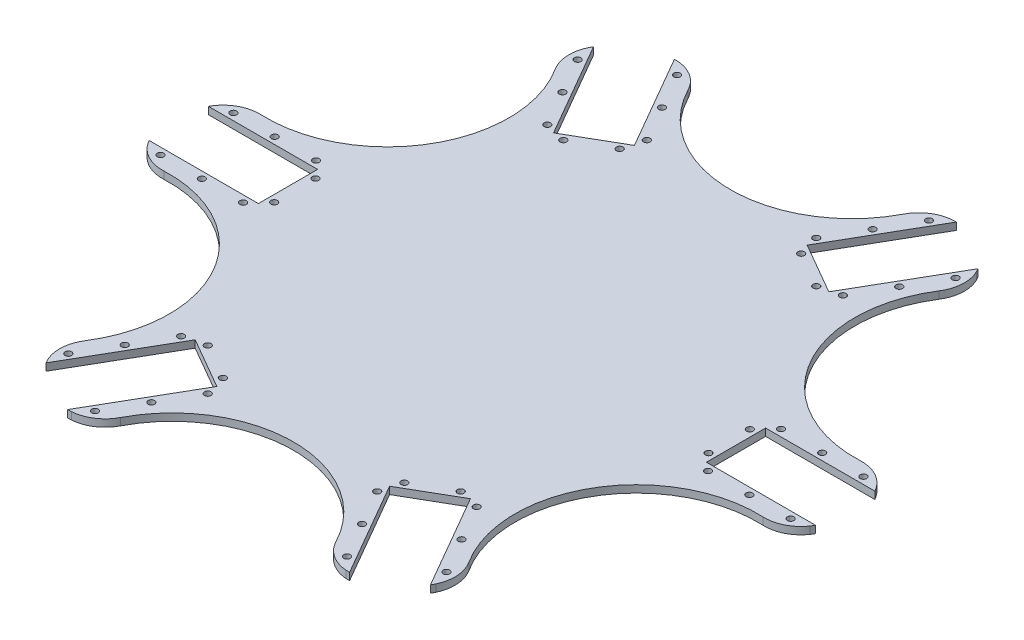
SolidWorks part; units mm, degrees
material "1060-H12"
ref_plane "Front Plane" through (0, 0, 0) normal (0, 0, 1) x (1, 0, 0)
ref_plane "Top Plane" through (0, 0, 0) normal (0, 1, 0) x (1, 0, 0)
ref_plane "Right Plane" through (0, 0, 0) normal (1, 0, 0) x (0, 0, -1)
sketch "Sketch2" plane through (0, 0, 0) normal (0, 1, 0) x (1, 0, 0)
  line L1 (0, 125) -> (-58.0814, 125)
  line L2 (-35.5814, 86.0289) -> (-56.7125, 73.8289)
  line L3 (-79.2125, 112.8) -> (-108.2532, 62.5)
  line L4 (-35.5814, 86.0289) -> (-58.0814, 125)
  line L7 (0, 0) -> (0, 125)
  line L8 (0, 0) -> (-108.2532, 62.5)
  line L12 (-79.2125, 112.8) -> (-56.7125, 73.8289)
  circle A0 centre (-37.3857, 81.754) radius 1.35
  circle A1 centre (-52.1082, 73.254) radius 1.35
  circle A2 centre (-60.8873, 75.4599) radius 1.35
  circle A3 centre (-34.9066, 90.4599) radius 1.35
  circle A4 centre (-51.9066, 119.9048) radius 1.35
  circle A5 centre (-43.4066, 105.1824) radius 1.35
  circle A6 centre (-69.3873, 90.1824) radius 1.35
  circle A7 centre (-77.8873, 104.9048) radius 1.35
  dimension "D3" = 3.5
  dimension "D5" = 2.8
  dimension "D9" = 34
  dimension "D13" = 2.8
  dimension "D14" = 2.8
  dimension "D2" = 3.5
  dimension "D4" = 17
  dimension "D6" = 2.8
  dimension "D12" = 17
  dimension "D15" = 17
  dimension "D16" = 34
extrude "Boss-Extrude1" add sketch "Sketch2" along normal blind 3
pattern_circular "CirPattern1" count 6 over 360 about axis through (0, 3, 0) along (0, -1, 0) of "Boss-Extrude1"
sketch "Sketch4" plane through (0, 3, 0) normal (0, 1, 0) x (1, 0, 0)
  line L0 (58.0814, 125) -> (-58.0814, 125) construction
  line L1 (137.2939, 12.2) -> (79.2125, 112.8) construction
  line L2 (79.2125, -112.8) -> (137.2939, -12.2) construction
  line L3 (-58.0814, -125) -> (58.0814, -125) construction
  line L4 (-137.2939, -12.2) -> (-79.2125, -112.8) construction
  line L5 (-79.2125, 112.8) -> (-137.2939, 12.2) construction
  line L6 (79.2125, -112.8) -> (137.2939, -12.2)
  line L8 (137.2939, 12.2) -> (79.2125, 112.8)
  line L10 (58.0814, 125) -> (-58.0814, 125)
  line L12 (-79.2125, 112.8) -> (-137.2939, 12.2)
  line L14 (-92.2939, -12.2) -> (-137.2939, -12.2) construction
  line L15 (-137.2939, -12.2) -> (-79.2125, -112.8)
  line L17 (-58.0814, -125) -> (58.0814, -125)
  arc A0 (-30.9451, 108.6476) -> (30.9451, 108.6476) centre (0, 125) ccw
  arc A1 (78.619, 81.123) -> (109.5641, 27.5246) centre (108.2532, 62.5) ccw
  arc A2 (109.5641, -27.5246) -> (78.619, -81.123) centre (108.2532, -62.5) ccw
  arc A4 (-78.619, -81.123) -> (-109.5641, -27.5246) centre (-108.2532, -62.5) ccw
  arc A5 (-109.5641, 27.5246) -> (-78.619, 81.123) centre (-108.2532, 62.5) ccw
  arc A6 (58.0814, 125) -> (30.9451, 108.6476) centre (58.0814, 94.3078) ccw
  arc A7 (-30.9451, 108.6476) -> (-58.0814, 125) centre (-58.0814, 94.3078) ccw
  arc A8 (-79.2125, 112.8) -> (-78.619, 81.123) centre (-52.6322, 97.4539) ccw
  arc A9 (-109.5641, 27.5246) -> (-137.2939, 12.2) centre (-110.7137, -3.1461) ccw
  arc A10 (109.5641, -27.5246) -> (137.2939, -12.2) centre (110.7137, 3.1461) ccw
  arc A11 (-58.0814, -125) -> (-30.9451, -108.6476) centre (-58.0814, -94.3078) ccw
  arc A12 (-78.619, -81.123) -> (-79.2125, -112.8) centre (-52.6322, -97.4539) ccw
  arc A13 (-137.2939, -12.2) -> (-109.5641, -27.5246) centre (-110.7137, 3.1461) ccw
  arc A14 (78.619, 81.123) -> (79.2125, 112.8) centre (52.6322, 97.4539) ccw
  arc A16 (79.2125, -112.8) -> (78.619, -81.123) centre (52.6322, -97.4539) ccw
  arc A19 (137.2939, 12.2) -> (109.5641, 27.5246) centre (110.7137, -3.1461) ccw
  arc A20 (30.9451, -108.6476) -> (-30.9451, -108.6476) centre (0, -125) ccw
  arc A21 (30.9451, -108.6476) -> (58.0814, -125) centre (58.0814, -94.3078) ccw
extrude "Cut-Extrude3" cut sketch "Sketch4" against normal blind 5
sketch "Sketch9" plane through (0, 3, 0) normal (0, 1, 0) x (1, 0, 0)
  line L0 (-46.1469, 79.9289) -> (-62.6469, 108.5077) construction
  line L1 (-58.0814, 125) -> (58.0814, 125)
  line L2 (79.2125, 112.8) -> (137.2939, 12.2)
  line L3 (-35.5814, 86.0289) -> (-56.7125, 73.8289) construction
  line L4 (137.2939, -12.2) -> (79.2125, -112.8)
  line L5 (46.1469, 79.9289) -> (62.6469, 108.5077) construction
  line L6 (56.7125, 73.8289) -> (35.5814, 86.0289) construction
  line L7 (58.0814, -125) -> (-58.0814, -125)
  line L8 (-79.2125, -112.8) -> (-137.2939, -12.2)
  line L9 (-137.2939, 12.2) -> (-79.2125, 112.8)
  arc A0 (-44.3583, 116.9275) -> (44.3583, 116.9275) centre (0, 140) ccw
  arc A1 (-44.3583, 116.9275) -> (-58.0814, 125) centre (-57.6658, 110.0058) ccw
  circle A2 centre (-62.6469, 108.5077) radius 25 construction
  circle A3 centre (62.6469, 108.5077) radius 25 construction
  arc A4 (-30.9451, 108.6476) -> (30.9451, 108.6476) centre (0, 125) ccw construction
  arc A5 (58.0814, 125) -> (44.3583, 116.9275) centre (57.6658, 110.0058) ccw
  arc A6 (79.083, 96.8792) -> (79.2125, 112.8) centre (66.4349, 104.9429) ccw
  arc A7 (79.083, 96.8792) -> (123.4413, 20.0483) centre (121.2436, 70) ccw
  arc A8 (137.2939, 12.2) -> (123.4413, 20.0483) centre (124.1007, 5.0628) ccw
  arc A9 (123.4413, -20.0483) -> (137.2939, -12.2) centre (124.1007, -5.0628) ccw
  arc A10 (123.4413, -20.0483) -> (79.083, -96.8792) centre (121.2436, -70) ccw
  arc A11 (79.2125, -112.8) -> (79.083, -96.8792) centre (66.4349, -104.9429) ccw
  arc A12 (44.3583, -116.9275) -> (58.0814, -125) centre (57.6658, -110.0058) ccw
  arc A13 (44.3583, -116.9275) -> (-44.3583, -116.9275) centre (0, -140) ccw
  arc A14 (-58.0814, -125) -> (-44.3583, -116.9275) centre (-57.6658, -110.0058) ccw
  arc A15 (-79.083, -96.8792) -> (-79.2125, -112.8) centre (-66.4349, -104.9429) ccw
  arc A16 (-79.083, -96.8792) -> (-123.4413, -20.0483) centre (-121.2436, -70) ccw
  arc A17 (-137.2939, -12.2) -> (-123.4413, -20.0483) centre (-124.1007, -5.0628) ccw
  arc A18 (-123.4413, 20.0483) -> (-137.2939, 12.2) centre (-124.1007, 5.0628) ccw
  arc A19 (-123.4413, 20.0483) -> (-79.083, 96.8792) centre (-121.2436, 70) ccw
  arc A20 (-79.2125, 112.8) -> (-79.083, 96.8792) centre (-66.4349, 104.9429) ccw
  point P8 (0, 90)
  point P61 (0, 0)
  dimension "D1" = 6
extrude "Cut-Extrude9" cut sketch "Sketch9" against normal blind 10 contours A5 L1 A1 A0 | A20 L9 A18 A19 | A17 L8 A15 A16 | A8 L2 A6 A7 | A11 L4 A9 A10 | A14 L7 A12 A13 region at (0, 3, -110.6371) region at (95.8145, 3, -55.3185) region at (95.8145, 3, 55.3185) region at (0, 3, 110.6371) region at (-95.8145, 3, 55.3185) region at (-95.8145, 3, -55.3185)
sketch "Sketch10" plane through (0, 0, 0) normal (0, -1, 0) x (-1, 0, 0)
  circle A0 centre (0, 0) radius 44.6177 construction
sketch "Sketch11" plane through (0, 0, 0) normal (1, 0, 0) x (0, 0, -1)
  line L0 (0, 0) -> (0, 3) construction
  line L1 (-12.2, 3) -> (12.2, 3) construction
